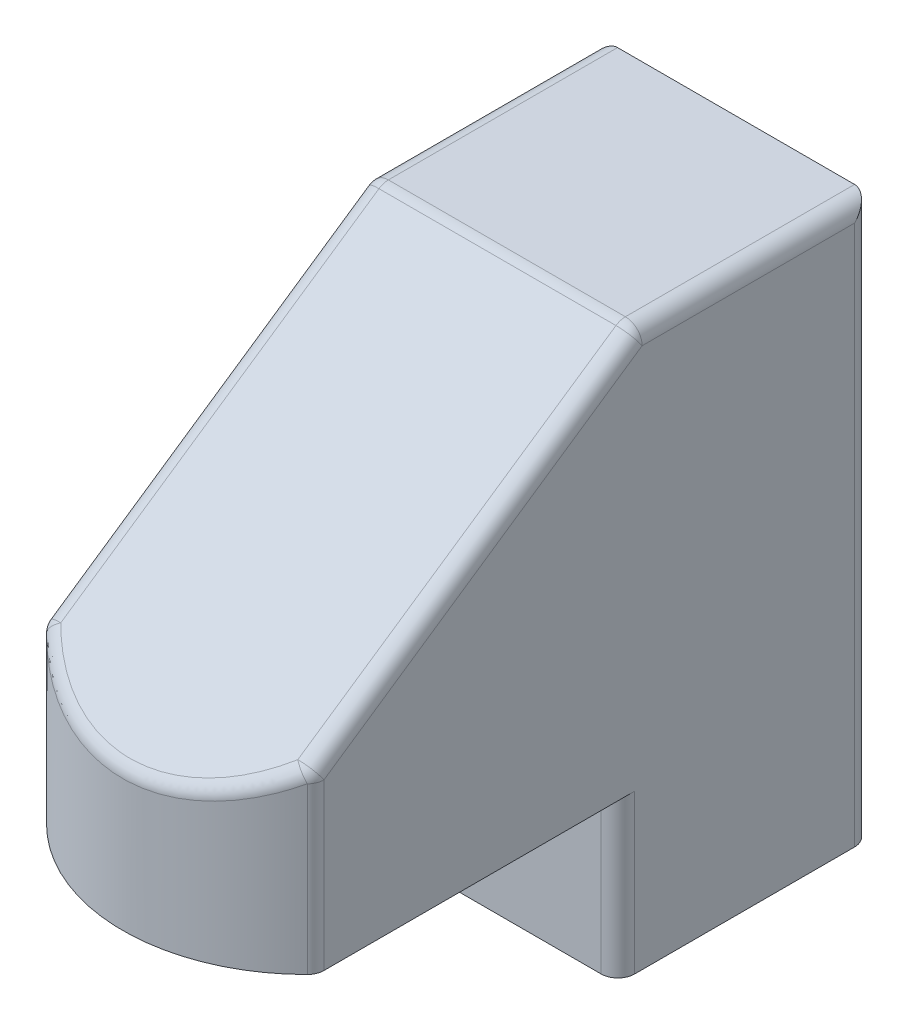
SolidWorks part; units mm, degrees
ref_plane "Front Plane" through (0, 0, 0) normal (0, 0, 1) x (1, 0, 0)
ref_plane "Top Plane" through (0, 0, 0) normal (0, 1, 0) x (1, 0, 0)
ref_plane "Right Plane" through (0, 0, 0) normal (1, 0, 0) x (0, 0, -1)
sketch "Sketch1" plane through (0, 0, 0) normal (0, 1, 0) x (1, 0, 0)
  line L0 (0, 0) -> (8.08, 0)
  line L1 (8.08, 0) -> (8.08, -16.55)
  line L2 (0, 0) -> (0, -16.55)
  line L3 (4.04, -18.32) -> (-7.2213, -18.32) construction
  arc A0 (0, -16.55) -> (8.08, -16.55) centre (4.04, -12.8244) ccw
  dimension "D3" = 18.32
  dimension "D1" = 8.08
  dimension "D2" = 16.55
extrude "Boss-Extrude1" add sketch "Sketch1" along normal blind 11.91
sketch "Sketch2" plane through (8.08, 0, 0) normal (1, 0, 0) x (0, 0, -1)
  line L0 (-7, 11.91) -> (-16.55, 5.4)
  line L1 (-16.55, 11.91) -> (0, 11.91) construction
  line L2 (-16.55, 11.91) -> (-16.55, 0) construction
  line L3 (0, 11.91) -> (0, 0) construction
  line L4 (-16.55, 0) -> (0, 0) construction
  line L5 (-16.55, 5.4) -> (-22.0573, 1.6458)
  line L6 (-22.0573, 1.6458) -> (-22.0573, 16.5751)
  line L7 (-22.0573, 16.5751) -> (-7, 16.5751)
  line L8 (-7, 16.5751) -> (-7, 11.91)
  dimension "D1" = 7
  dimension "D2" = 5.4
extrude "Cut-Extrude1" cut sketch "Sketch2" against normal up to surface (8.08 mm away) up to face at (0, 5.955, 8.275)
sketch "Sketch3" plane through (0, 0, 0) normal (0, -1, 0) x (1, 0, 0)
  line L0 (0, 0) -> (0, 16.55) construction
  line L1 (8.08, 0) -> (0, 0)
  line L2 (8.08, 0) -> (8.08, 7.57)
  line L3 (8.08, 7.57) -> (0, 7.57)
  line L4 (0, 0) -> (0, 7.57)
  dimension "D1" = 7.57
extrude "Boss-Extrude2" add sketch "Sketch3" along normal blind 4.73
sketch "Sketch4" plane through (0, 0, 0) normal (0, -1, 0) x (1, 0, 0)
  line L1 (8.08, 16.55) -> (8.08, 7.57) construction
  line L2 (8.08, 7.57) -> (0, 7.57) construction
  circle A0 centre (4.04, 11.32) radius 2.945
  point P6 (5.0009, 10.837)
  dimension "D1" = 5.89
  dimension "D2" = 4.04
  dimension "D3" = 3.75
extrude "Boss-Extrude3" add sketch "Sketch4" along normal blind 0.64
sketch "Sketch5" plane through (0, -4.73, 0) normal (0, -1, 0) x (1, 0, 0)
  line L0 (8.08, 0) -> (8.08, 7.57) construction
  line L1 (0, 0) -> (8.08, 0) construction
  circle A0 centre (4.04, 3.785) radius 2.175
  dimension "D1" = 4.35
  dimension "D2" = 4.04
  dimension "D3" = 3.785
extrude "Cut-Extrude2" cut sketch "Sketch5" against normal blind 13.11
fillet "Fillet1" radius 0.5 12 edges at (0, -2.365, 7.57) (8.08, -2.365, 7.57) (8.08, 3.59, 0) (0, 3.59, 0) (0, 11.91, 3.5) (4.04, 11.91, 7) (8.08, 11.91, 3.5) (8.08, 2.7, 16.55) (0, 2.7, 16.55) (4.04, 4.1934, 18.32) (8.08, 8.655, 11.775) (0, 8.655, 11.775)
